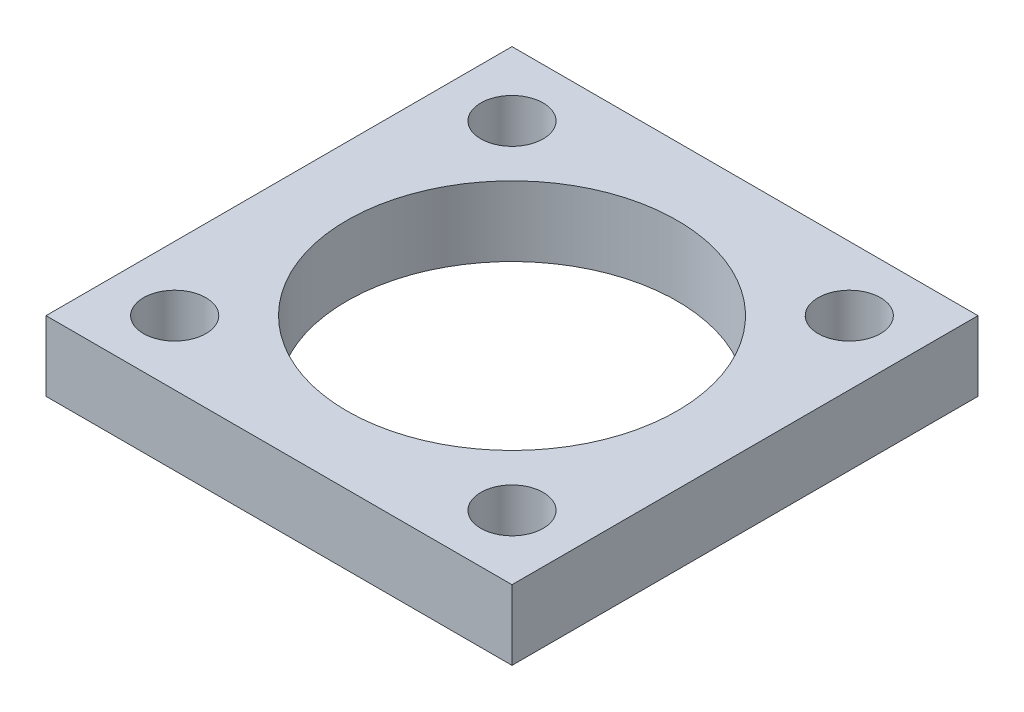
SolidWorks part; units mm, degrees
ref_plane "Front Plane" through (0, 0, 0) normal (0, 0, 1) x (1, 0, 0)
ref_plane "Top Plane" through (0, 0, 0) normal (0, 1, 0) x (1, 0, 0)
ref_plane "Right Plane" through (0, 0, 0) normal (1, 0, 0) x (0, 0, -1)
sketch "Sketch2" plane through (0, 0, 0) normal (0, 1, 0) x (1, 0, 0)
  line L1 (-12.7, -12.7) -> (12.7, -12.7)
  line L2 (-12.7, -12.7) -> (-12.7, 12.7)
  line L3 (-12.7, 12.7) -> (12.7, 12.7)
  line L4 (12.7, -12.7) -> (12.7, 12.7)
  line L5 (-12.7, -12.7) -> (12.7, 12.7) construction
  line L6 (-12.7, 12.7) -> (12.7, -12.7) construction
  point P0 (0, 0)
  dimension "D2" = 25.4
extrude "Boss-Extrude1" add sketch "Sketch2" along normal blind 3.81
sketch "Sketch4" plane through (0, 3.81, 0) normal (0, 1, 0) x (1, 0, 0)
  line L0 (-9.1924, 9.1924) -> (9.1924, -9.1924) construction
  line L1 (-9, 0) -> (9, 0) construction
  line L2 (9.1924, 9.1924) -> (-9.1924, -9.1924) construction
  circle A0 centre (0, 0) radius 9
  point P9 (0, 0)
  point P10 (9.1924, 9.1924)
  point P11 (-9.1924, -9.1924)
  point P12 (0, 0)
  point P13 (0, 0)
  dimension "D3" = 18
  dimension "D1" = 26
  dimension "D2" = 45
  dimension "D4" = 45
extrude "Cut-Extrude1" cut sketch "Sketch4" against normal through all
hole_wizard "M3 Clearance Hole2" positions "3DSketch5" profile "Sketch9" hole size "M3" standard "ANSI Metric" end condition through all
sketch3d "3DSketch5"
  point P0 (-9.1924, 3.81, -9.1924)
  point P3 (9.1924, 3.81, 9.1924)
  point P6 (9.1924, 3.81, -9.1924)
  point P9 (-9.1924, 3.81, 9.1924)
sketch "Sketch9" plane through (-9.1924, 3.81, -9.1924) normal (1, 0, 0) x (0, 0, 1)
  line L0 (0, 0) -> (0, 3.81)
  line L1 (0, 3.81) -> (1.7, 3.81)
  line L2 (1.7, 3.81) -> (1.7, 0)
  line L5 (1.7, 0) -> (0, 0)
  line L11 (0, -6.35) -> (0, 107.95) construction
  dimension "Thru Hole Dia." = 3.4
  dimension "Thru Hole Depth" = 3.81
